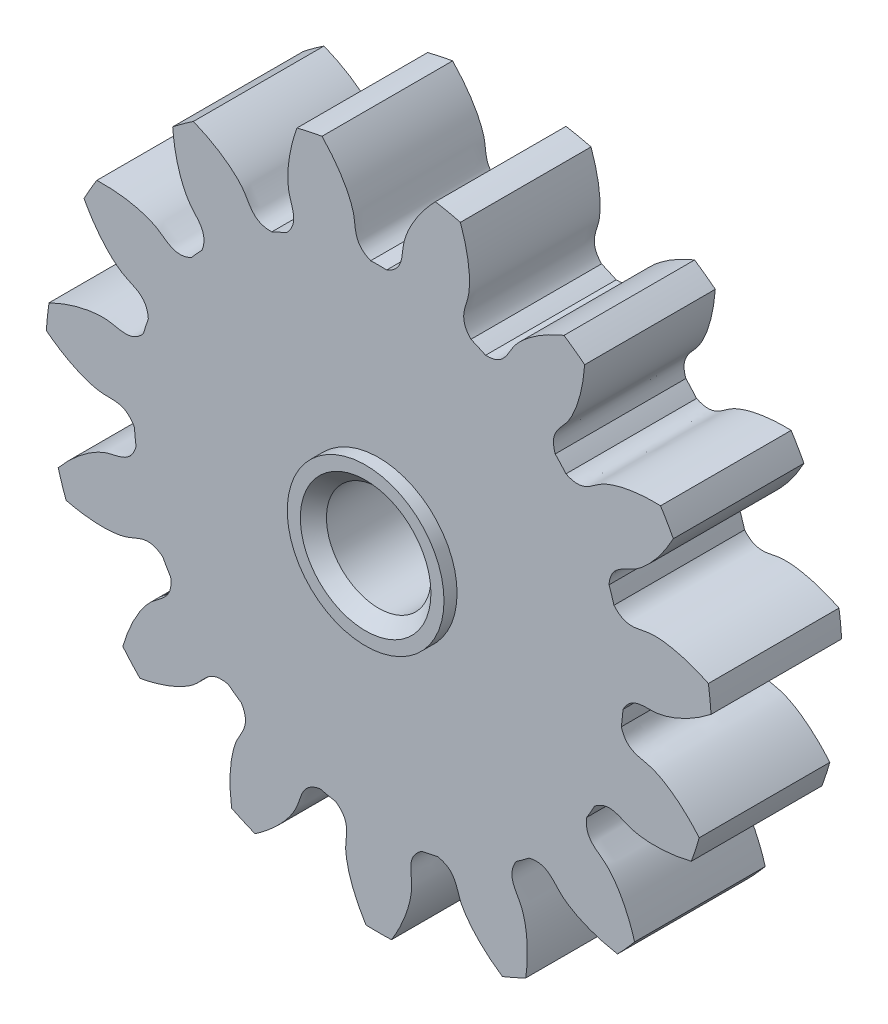
SolidWorks part; units mm, degrees
ref_plane "前视基准面" through (0, 0, 0) normal (0, 0, 1) x (1, 0, 0)
ref_plane "上视基准面" through (0, 0, 0) normal (0, 1, 0) x (1, 0, 0)
ref_plane "右视基准面" through (0, 0, 0) normal (1, 0, 0) x (0, 0, -1)
sketch "草图1" plane through (0, 0, 0) normal (0, 0, 1) x (1, 0, 0)
  circle A0 centre (0, 0) radius 12.75
extrude "凸台-拉伸1" add sketch "草图1" along normal blind 5
ref_axis "基准轴1" through (0, 0, -0.25) along (0, 0, 1)
sketch "草图2" plane through (0, 0, 0) normal (0, 0, 1) x (1, 0, 0)
  line L0 (0, 0) -> (0, 12.75) construction
  circle A0 centre (0, 0) radius 12.75 construction
  arc A1 (0.3064, 9.37) -> (-0.3064, 9.37) centre (0, 0) ccw
  arc A2 (4.8703, 14.4539) -> (-4.8703, 14.4539) centre (0, 0) ccw
  spline S0 degree 3 poles (0.3064, 9.37) (0.9858, 9.6516) (0.8582, 10.1795) (0.9769, 10.6628) (0.9861, 10.6975) (0.9973, 10.7361) (1.0104, 10.7785) (1.0257, 10.8247) (1.0434, 10.8745) (1.0635, 10.9279) (1.0863, 10.9848) (1.1118, 11.0452) (1.1403, 11.1089) (1.1718, 11.1759) (1.2066, 11.2459) (1.2447, 11.3191) (1.2863, 11.3952) (1.3315, 11.474) (1.3804, 11.5556) (1.4332, 11.6398) (1.49, 11.7265) (1.5509, 11.8155) (1.616, 11.9067) (1.6855, 11.9999) (1.7594, 12.0951) (1.8379, 12.1921) (1.921, 12.2907) (2.0088, 12.3909) (2.1015, 12.4924) (2.1991, 12.595) (2.3018, 12.6987) (2.4095, 12.8033) (2.5223, 12.9086) (2.6404, 13.0144) (2.7638, 13.1206) (2.8926, 13.227) (3.0268, 13.3335) (3.1664, 13.4398) (3.3116, 13.5458) (3.4623, 13.6512) (3.6186, 13.7561) (3.7805, 13.86) (3.948, 13.9629) (4.1213, 14.0646) (4.3002, 14.1648) (4.5489, 14.2977) (4.7402, 14.3926) (4.8703, 14.4539) knots 0 0 0 0 0.202473 0.206979 0.212085 0.217793 0.224101 0.23101 0.23852 0.24663 0.255341 0.264653 0.274566 0.285079 0.296194 0.307909 0.320225 0.333141 0.346659 0.360777 0.375496 0.390816 0.406736 0.423257 0.440379 0.458102 0.476426 0.49535 0.514875 0.535001 0.555728 0.577055 0.598984 0.621513 0.644642 0.668373 0.692704 0.717636 0.743169 0.769303 0.796037 0.823373 0.851309 0.879845 0.908983 0.938721 1 1 1 1
  spline S1 degree 3 poles (-0.3064, 9.37) (-0.9858, 9.6516) (-0.8582, 10.1795) (-0.9769, 10.6628) (-0.9861, 10.6975) (-0.9973, 10.7361) (-1.0104, 10.7785) (-1.0257, 10.8247) (-1.0434, 10.8745) (-1.0635, 10.9279) (-1.0863, 10.9848) (-1.1118, 11.0452) (-1.1403, 11.1089) (-1.1718, 11.1759) (-1.2066, 11.2459) (-1.2447, 11.3191) (-1.2863, 11.3952) (-1.3315, 11.474) (-1.3804, 11.5556) (-1.4332, 11.6398) (-1.49, 11.7265) (-1.5509, 11.8155) (-1.616, 11.9067) (-1.6855, 11.9999) (-1.7594, 12.0951) (-1.8379, 12.1921) (-1.921, 12.2907) (-2.0088, 12.3909) (-2.1015, 12.4924) (-2.1991, 12.595) (-2.3018, 12.6987) (-2.4095, 12.8033) (-2.5223, 12.9086) (-2.6404, 13.0144) (-2.7638, 13.1206) (-2.8926, 13.227) (-3.0268, 13.3335) (-3.1664, 13.4398) (-3.3116, 13.5458) (-3.4623, 13.6512) (-3.6186, 13.7561) (-3.7805, 13.86) (-3.948, 13.9629) (-4.1213, 14.0646) (-4.3002, 14.1648) (-4.5489, 14.2977) (-4.7402, 14.3926) (-4.8703, 14.4539) knots 0 0 0 0 0.202473 0.206979 0.212085 0.217793 0.224101 0.23101 0.23852 0.24663 0.255341 0.264653 0.274566 0.285079 0.296194 0.307909 0.320225 0.333141 0.346659 0.360777 0.375496 0.390816 0.406736 0.423257 0.440379 0.458102 0.476426 0.49535 0.514875 0.535001 0.555728 0.577055 0.598984 0.621513 0.644642 0.668373 0.692704 0.717636 0.743169 0.769303 0.796037 0.823373 0.851309 0.879845 0.908983 0.938721 1 1 1 1
extrude "切除-拉伸1" cut sketch "草图2" along normal through all
pattern_circular "阵列(圆周)1" count 15 every 24 about axis through (0, 0, -0.25) along (0, 0, 1) of "切除-拉伸1"
sketch "草图3" plane through (0, 0, 0) normal (0, 0, 1) x (1, 0, 0)
  circle A0 centre (0, 0) radius 11.25 construction
  dimension "Dn" = 22.5
sketch "草图4" plane through (0, 0, 5) normal (0, 0, 1) x (1, 0, 0)
  circle A0 centre (0, 0) radius 2
  dimension "D1" = 4
extrude "切除-拉伸2" cut sketch "草图4" against normal through all
sketch "草图5" plane through (0, 0, 5) normal (0, 0, 1) x (1, 0, 0)
  circle A0 centre (0, 0) radius 2 construction
  circle A1 centre (0, 0) radius 2
  circle A2 centre (0, 0) radius 3
  dimension "D1" = 6
extrude "凸台-拉伸2" add sketch "草图5" along normal blind 0.5
chamfer "倒角1" distance 0.5 angle 45 2 edges at (2, 0, 0) (2, 0, 5.5)
